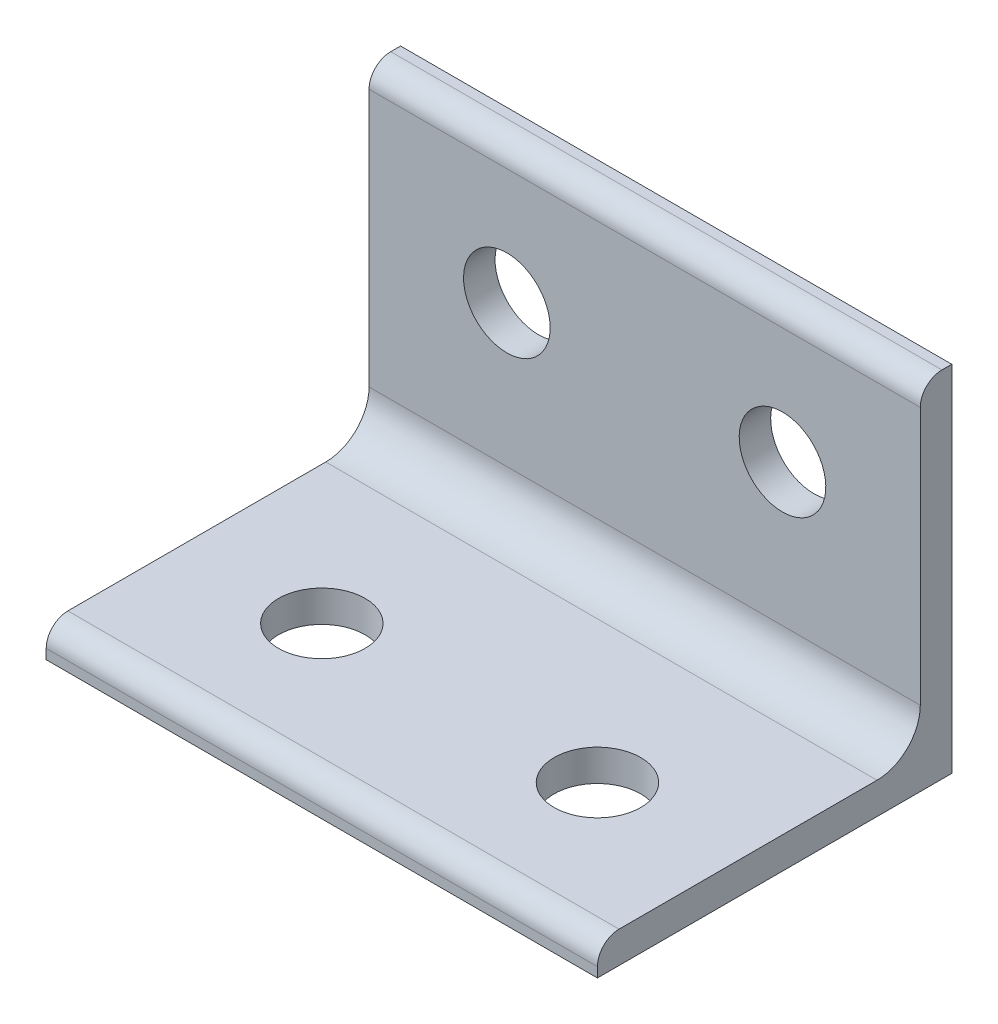
SolidWorks part; units mm, degrees
note: '?' marks a value the reader was unsure of.
other "Connection Feature"
ref_plane "Front Plane" through (0, 0, 0) normal (0, 0, 1) x (1, 0, 0)
ref_plane "Top Plane" through (0, 0, 0) normal (0, 1, 0) x (1, 0, 0)
ref_plane "Right Plane" through (0, 0, 0) normal (1, 0, 0) x (0, 0, -1)
ref_axis "Axis1" through (-18.99, 0, 0) along (1, 0, 0)?
sketch "Sketch1" plane through (0, 0, 0) normal (0, 0, 1) x (1, 0, 0)
  line L0 (0, 0) -> (140, 0)
  dimension "D1" = 140
other "Angles equal 90 X 90 X 8(1)"
ref_plane "Plane1" through (0, 45, 45) normal (1, 0, 0) x (0, 1, 0)
sketch "Sketch11" plane through (0, 45, 45) normal (1, 0, 0) x (0, 1, 0)
  line L0 (-45, 45) -> (-45, -45)
  line L1 (-45, -45) -> (45, -45) construction
  line L2 (-45, -45) -> (-45, 45) construction
  line L3 (-45, 45) -> (45, 45) construction
  line L4 (45, -45) -> (45, 45) construction
  line L5 (-45, -45) -> (45, 45) construction
  line L6 (-45, 45) -> (45, -45) construction
  line L7 (-45, -45) -> (45, -45)
  line L8 (45, -45) -> (45, -42.5)
  line L9 (39.5, -37) -> (-26, -37)
  line L10 (-37, -26) -> (-37, 39.5)
  line L11 (-42.5, 45) -> (-45, 45)
  arc A0 (-26, -37) -> (-37, -26) centre (-26, -26) cw
  arc A1 (-37, 39.5) -> (-42.5, 45) centre (-42.5, 39.5) ccw
  arc A2 (45, -42.5) -> (39.5, -37) centre (39.5, -42.5) ccw
  point P0 (0, 0)
  point P13 (-37, 45)
  point P16 (45, -37)
  point P17 (-45, 0)
  point P18 (-45, 45)
  point P19 (0, -45)
  point P20 (-45, -45)
  point P21 (0, 0)
  point P22 (45, -45)
  point P23 (45, 0)
  point P24 (45, 45)
  point P25 (0, 45)
  point P26 (0, 0)
  dimension "r1" = 11
  dimension "r2" = 5.5
  dimension "hxb" = 90
  dimension "t" = 8
sketch "Sketch12" plane through (0, 0, 0) normal (0, 1, 0) x (1, 0, 0)
  line L2 (0, -49.5) -> (0, 49.5) construction
  line L3 (-49.5, 0) -> (49.5, 0) construction
  circle A0 centre (35, -55) radius 11
  dimension "D1" = 22
  dimension "D2" = 35
  dimension "D3" = 55
extrude "Cut-Extrude1" cut sketch "Sketch12" along normal through all both and the other way through all
pattern_linear "LPattern1" count 2 spacing 70 along (1, 0, 0) of "Cut-Extrude1"
pattern_circular "CirPattern4" count 2 every 90 about axis through (-18.99, 0, 0) along (1, 0, 0) of "LPattern1", "Cut-Extrude1"
equation "\"Length\"= ( \"Number of Holes\" - 1 ) * \"Hole Pitch\" + \"Hole End Distance\" * 2"
equation "\"Hole Dia\"= 22"
equation "\"Hole Pitch\"= 70"
equation "\"G Back Mark\"= 55"
equation "\"Hole End Distance\"=35"
equation "\"D1@Sketch12\"=\"Hole Dia\""
equation "\"D3@LPattern1\"= \"Hole Pitch\""
equation "\"Number of Holes\"= 2"
equation "\"D1@LPattern1\"= \"Number of Holes\""
equation "\"D2@Sketch12\"=\"Hole End Distance\""
equation "\"D3@Sketch12\"=\"G Back Mark\""
equation "\"D1@Sketch1\"=\"Length\""
